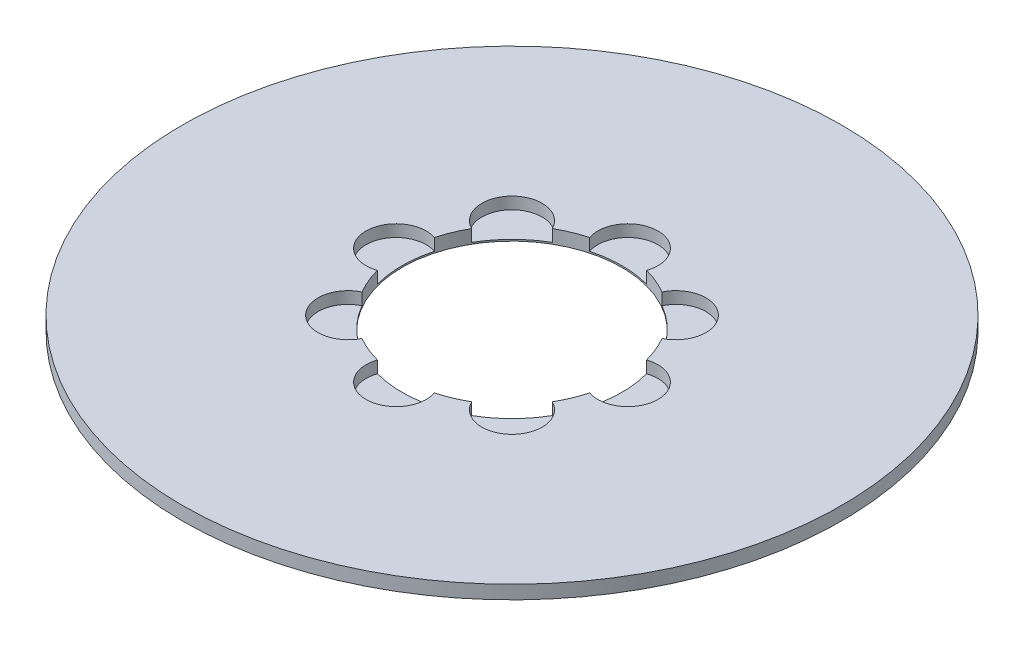
SolidWorks part; units mm, degrees
ref_plane "Front Plane" through (0, 0, 0) normal (0, 0, 1) x (1, 0, 0)
ref_plane "Top Plane" through (0, 0, 0) normal (0, 1, 0) x (1, 0, 0)
ref_plane "Right Plane" through (0, 0, 0) normal (1, 0, 0) x (0, 0, -1)
sketch "Sketch1" plane through (0, 0, 0) normal (0, 1, 0) x (1, 0, 0)
  circle A0 centre (0, 0) radius 97.5
  dimension "FLANGE_OD" = 195
extrude "Boss-Extrude1" add sketch "Sketch1" along normal blind 4
sketch "Sketch2" plane through (0, 0, 0) normal (0, 1, 0) x (1, 0, 0)
  circle A0 centre (0, 0) radius 32.5
  dimension "BORE_D" = 65
extrude "Cut-Extrude1" cut sketch "Sketch2" along normal through all
sketch "Sketch3" plane through (0, 4, 0) normal (0, 1, 0) x (1, 0, 0)
  circle A0 centre (0, 0) radius 34.2775 construction
  circle A1 centre (-34.2775, 0) radius 8.9053
  dimension "BOLT_D" = 17.8106
  dimension "BOLT_PCD" = 68.555
extrude "Cut-Extrude2" cut sketch "Sketch3" against normal blind 3.5313
pattern_circular "CirPattern1" count 8 over 360 about axis through (0, 0, 0) along (0, 1, 0) of "Cut-Extrude2"
